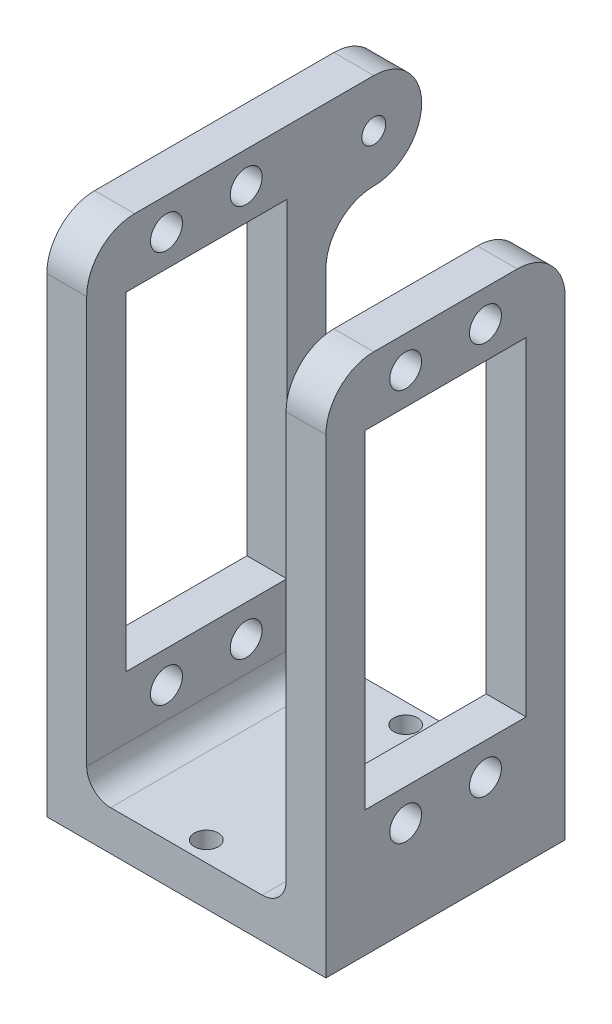
SolidWorks part; units mm, degrees
ref_plane "Front Plane" through (0, 0, 0) normal (0, 0, 1) x (1, 0, 0)
ref_plane "Top Plane" through (0, 0, 0) normal (0, 1, 0) x (1, 0, 0)
ref_plane "Right Plane" through (0, 0, 0) normal (1, 0, 0) x (0, 0, -1)
sketch "Sketch1" plane through (0, 0, 0) normal (0, 1, 0) x (1, 0, 0)
  line L1 (0, 0) -> (35, 0)
  line L2 (0, 0) -> (0, 30)
  line L3 (0, 30) -> (35, 30)
  line L4 (35, 0) -> (35, 30)
  dimension "D1" = 35
  dimension "D2" = 30
extrude "Boss-Extrude3" add sketch "Sketch1" along normal blind 5
sketch "Sketch5" plane through (0, 5, 0) normal (0, 1, 0) x (1, 0, 0)
  line L0 (0, 0) -> (35, 0) construction
  line L1 (0, 30) -> (5, 30)
  line L2 (0, 30) -> (0, 0)
  line L3 (0, 0) -> (5, 0)
  line L4 (5, 30) -> (5, 0)
  line L6 (35, 30) -> (30, 30)
  line L7 (35, 30) -> (35, 0)
  line L8 (35, 0) -> (30, 0)
  line L9 (30, 30) -> (30, 0)
  dimension "D1" = 5
  dimension "D2" = 5
extrude "Boss-Extrude4" add sketch "Sketch5" along normal blind 60
sketch "Sketch6" plane through (35, 0, 0) normal (1, 0, 0) x (0, 0, -1)
  line L0 (30, 65) -> (30, 0) construction
  line L1 (4.9, 57) -> (25.1, 57)
  line L2 (4.9, 57) -> (4.9, 15.8)
  line L3 (4.9, 15.8) -> (25.1, 15.8)
  line L4 (25.1, 57) -> (25.1, 15.8)
  line L8 (0, 65) -> (30, 65) construction
  circle A0 centre (10, 61) radius 2
  circle A1 centre (20, 61) radius 2
  circle A2 centre (10, 11.8) radius 2
  circle A3 centre (20, 11.8) radius 2
  dimension "D6" = 4
  dimension "D7" = 4
  dimension "D11" = 4
  dimension "D12" = 4
  dimension "D1" = 41.2
  dimension "D2" = 20.2
  dimension "D3" = 4.9
  dimension "D4" = 4
  dimension "D5" = 4
  dimension "D8" = 10
  dimension "D9" = 10
  dimension "D10" = 8
  dimension "D13" = 10
  dimension "D14" = 4
  dimension "D15" = 10
  dimension "D16" = 4
extrude "Cut-Extrude1" cut sketch "Sketch6" against normal blind 60
fillet "Fillet2" radius 3 2 edges at (30, 5, -15) (5, 5, -15)
sketch "Sketch8" plane through (0, 0, 0) normal (-1, 0, 0) x (0, 0, 1)
  line L1 (-30, 65) -> (-36, 65)
  line L2 (-30, 65) -> (-30, 53)
  line L3 (-30, 53) -> (-36, 53)
  line L4 (-36, 65) -> (-36, 53)
  circle A0 centre (-36, 59) radius 6
  circle A1 centre (-36, 59) radius 1.5
  line M16 (-30, 65) -> (-30, 0)
  dimension "D1" = 12
  dimension "D6" = 3
  dimension "D2" = 6
  dimension "D3" = 12
  dimension "D4" = 0
  dimension "D5" = 6
extrude "Boss-Extrude7" add sketch "Sketch8" against normal blind 5 contours A1 L4 A0 | A1 L4 A0 | A0 L1 M16 | A0 L3 L2 region at (0, 63.6598, -31.3402) region at (0, 59, -33.3262) region at (0, 59, -38.6738) region at (0, 54.3402, -31.3402)
fillet "Fillet3" radius 6 1 edges at (2.5, 53, -30)
sketch "Sketch10" plane through (0, 5, 0) normal (0, 1, 0) x (1, 0, 0)
  line L0 (8, 0) -> (27, 0) construction
  line L3 (8, 30) -> (8, 0) construction
  circle A0 centre (17.5, 27.5) radius 1.5
  circle A1 centre (17.5, 2.5) radius 1.5
  dimension "D1" = 3
  dimension "D2" = 3
  dimension "D3" = 25
  dimension "D4" = 2.5
  dimension "D5" = 9.5
  dimension "D6" = 9.5
extrude "Cut-Extrude2" cut sketch "Sketch10" against normal blind 5
fillet "Fillet4" radius 6 3 edges at (32.5, 65, -30) (32.5, 65, 0) (2.5, 65, 0)
